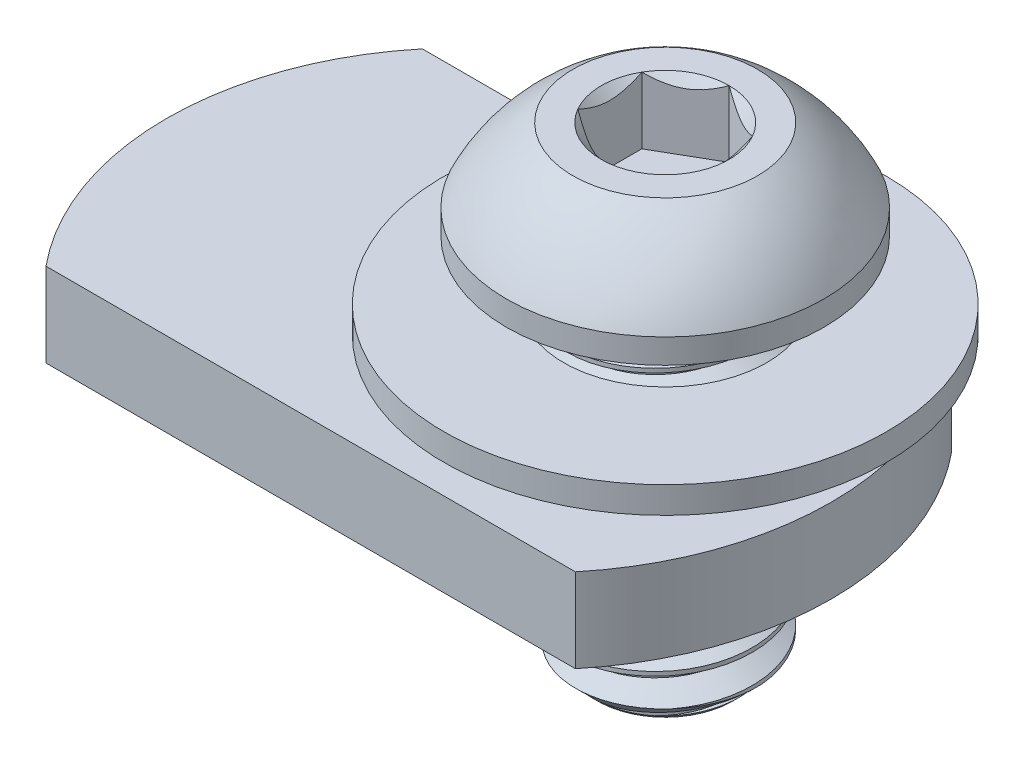
SolidWorks part; units mm, degrees
note: '?' marks a value the reader was unsure of.
ref_plane "Front Plane" through (0, 0, 0) normal (0, 0, 1) x (1, 0, 0)
ref_plane "Top Plane" through (0, 0, 0) normal (0, 1, 0) x (1, 0, 0)
ref_plane "Right Plane" through (0, 0, 0) normal (1, 0, 0) x (0, 0, -1)
sketch "Sketch1" plane through (0, 0, 0) normal (0, 1, 0) x (1, 0, 0)
  circle A0 centre (0, 0) radius 3.9688
  point P3 (-3.9688, 0)
  point P4 (3.9688, 0)
  dimension "D1" = 7.9375
extrude "Boss-Extrude1" add sketch "Sketch1" against normal blind 15.875
sketch "Sketch2" plane through (0, -15.875, 0) normal (0, -1, 0) x (1, 0, 0)
  circle A1 centre (0, 0) radius 3.9688
  circle A2 centre (0, 0) radius 3.9688
  point P0 (0, -3.9688)
  dimension "D1" = 0
curve "Helix/Spiral1" pitch 1.4111 height 17.2861 turns 12.25
sketch "Sketch3" plane through (0, 0, 0) normal (1, 0, 0) x (0, 0, -1)
  line L0 (4.1215, -15.7868) -> (2.8994, -16.4924) construction
  line L1 (2.8994, -16.4924) -> (4.1215, -17.1979) construction
  line L2 (4.1215, -17.1979) -> (4.1215, -15.7868) construction
  line L3 (3.0522, -16.4042) -> (3.0522, -16.5806) construction
  line L4 (3.9688, -15.875) -> (3.9688, -17.1097) construction
  line L5 (2.8994, -16.4924) -> (3.0522, -16.4924) construction
  line L6 (3.9688, -16.4924) -> (4.1215, -16.4924) construction
  line L8 (2.8994, -16.4924) -> (-3.9688, -16.4924) construction
  line L9 (3.0522, -16.4042) -> (4.0451, -15.8309)
  line L10 (3.0522, -16.4042) -> (3.0522, -16.5806)
  line L11 (3.0522, -16.5806) -> (4.0451, -17.1538)
  line L12 (4.0451, -17.1538) -> (4.0451, -15.8309)
  line L14 (-3.9688, -16.4924) -> (-3.9687, -15.0812) construction
  line L15 (-3.9687, -15.0812) -> (-3.9688, -13.6701) construction
  line L16 (-3.9688, -13.6701) -> (-3.9688, -12.259) construction
  line L17 (-3.9688, -12.259) -> (-3.9688, -10.8479) construction
  line L18 (-3.9688, 0) -> (-3.9688, -15.875) construction
  point P15 (4.0451, -16.4924)
  dimension "D1" = 1.4111
  dimension "D2" = 0.1764
sweep "Cut-Sweep1" cut profiles "Sketch3" path "Helix/Spiral1" align with end faces yes
sketch "Sketch4" plane through (0, -15.875, 0) normal (0, -1, 0) x (1, 0, 0)
  circle A0 centre (0, 0) radius 2.8994
extrude "Cut-Extrude1" cut sketch "Sketch4" against normal blind 1.4111 draft 45 flip side to cut
sketch "Sketch5" plane through (0, 0, 0) normal (0, 0, 1) x (1, 0, 0)
  line L0 (0, 0) -> (0, 4.2164)
  line L1 (-6.8199, 0) -> (0, 0)
  line L2 (0, 4.2164) -> (-3.9688, 4.2164)
  line L4 (-6.8199, 1.0541) -> (-6.8199, 0)
  line L5 (0, 0) -> (0, -15.875) construction
  arc A0 (-3.9688, 4.2164) -> (-6.8199, 1.0541) centre (0, -2.2283) ccw
  dimension "D1" = 4.2164
  dimension "D2" = 1.0541
  dimension "D4" = 13.6398
revolve "Revolve1" add sketch "Sketch5" angle 360 mid plane about L0
sketch "Sketch6" plane through (0, 4.2164, 0) normal (0, 1, 0) x (1, 0, 0)
  line L1 (0, 2.7496) -> (-2.3813, 1.3748)
  line L2 (-2.3813, 1.3748) -> (-2.3812, -1.3748)
  line L3 (-2.3812, -1.3748) -> (0, -2.7496)
  line L4 (0, -2.7496) -> (2.3813, -1.3748)
  line L5 (2.3813, -1.3748) -> (2.3812, 1.3748)
  line L6 (2.3812, 1.3748) -> (0, 2.7496)
  circle A0 centre (0, 0) radius 2.3813 construction
  dimension "D1" = 4.7625
extrude "Cut-Extrude2" cut sketch "Sketch6" against normal blind 2.8575
sketch "Sketch7" plane through (0, 4.2164, 0) normal (0, 1, 0) x (1, 0, 0)
  circle A0 centre (0, 0) radius 2.7496
extrude "Cut-Extrude3" cut sketch "Sketch7" against normal blind 2.8575 draft 45
sketch "Sketch8" plane through (0, 0, 0) normal (0, 1, 0) x (1, 0, 0)
  line L0 (-21.4376, 0) -> (0, 0) construction
  line L1 (0, 0) -> (7.1374, 0) construction
  line L2 (-18.5276, 8.0899) -> (4.2274, 8.0899)
  line L3 (-18.5276, -8.0899) -> (4.2274, -8.0899)
  line L4 (-21.4376, 8.0899) -> (7.1374, 8.0899) construction
  line L5 (-21.4376, 8.0899) -> (-21.4376, -8.0899) construction
  line L6 (-21.4376, -8.0899) -> (7.1374, -8.0899) construction
  line L7 (7.1374, 8.0899) -> (7.1374, -8.0899) construction
  arc A0 (-18.5276, 8.0899) -> (-18.5276, -8.0899) centre (-8.7376, 0) ccw
  arc A1 (4.2274, 8.0899) -> (4.2274, -8.0899) centre (-5.5626, 0) cw
  circle A3 centre (0, 0) radius 3.9688
  circle A4 centre (0, 0) radius 3.9688
  dimension "D2" = 28.575
  dimension "D5" = 12.7
  dimension "D6" = 12.7
  dimension "D3" = 16.1798
  dimension "D4" = 7.1374
  dimension "D1" = 0
extrude "Boss-Extrude2" add sketch "Sketch8" against normal blind 3.6068 from offset 6.35 separate body offset against normal yes
sketch "Sketch9" plane through (0, -9.9568, 0) normal (0, -1, 0) x (1, 0, 0)
  circle A1 centre (0, 0) radius 3.9688 construction
  circle A2 centre (0, 0) radius 3.9688
  circle A3 centre (0, 0) radius 4.5593
  dimension "D1" = 9.1186
extrude "Boss-Extrude3" add sketch "Sketch9" along normal blind 2.032
sketch "SketchZ" plane through (0, 0, 0) normal (0, 0, 1) x (1, 0, 0)
  line L0 (3.9688, -16.1396) -> (3.9688, -14.7285) construction
  line L2 (0, -16.4924) -> (0, -15.0812) construction
  line L4 (3.9688, -16.1396) -> (0, -16.1396) construction
  line L5 (0, -12.259) -> (0, -10.8479) construction
  line L6 (0, -15.7868) -> (0, -16.4924) construction
sketch "Sketch10" plane through (0, 0, 0) normal (0, 0, 1) x (1, 0, 0)
  line L0 (0, -15.875) -> (0, 0) construction
  line L1 (-9.5123, -2.54) -> (-4.3688, -2.54)
  line L2 (-9.5123, -2.54) -> (-9.5123, -3.683)
  line L3 (-9.5123, -3.683) -> (-4.3688, -3.683)
  line L4 (-4.3688, -2.54) -> (-4.3688, -3.683)
  line L6 (-6.8199, 0) -> (6.8199, 0) construction
  dimension "D1" = 19.0246
  dimension "D2" = 8.7376
  dimension "D3" = 1.143
  dimension "D4" = 2.54
revolve "Revolve2" add sketch "Sketch10" angle 360 mid plane about L0
ref_axis "Center Axis 1" through (0, 1.0541, 0) along (0, -1, 0)?
equation "\"D3@Helix/Spiral1\" = \"D4@Helix/Spiral1\" + \"D1@Boss-Extrude1\""
equation "\"D1@Sketch3\" = \"D4@Helix/Spiral1\""
equation "\"D2@Sketch3\" = \"D1@Sketch3\" / 8"
equation "\"D1@Cut-Extrude1\" = \"D4@Helix/Spiral1\""
equation "\"D1@Cut-Extrude2\" = \"D1@Sketch6\" * 3/5"
equation "\"D1@Cut-Extrude3\" = \"D1@Cut-Extrude2\""
equation "\"D2@Sketch5\" = \"D1@Sketch5\" * 1/4"
